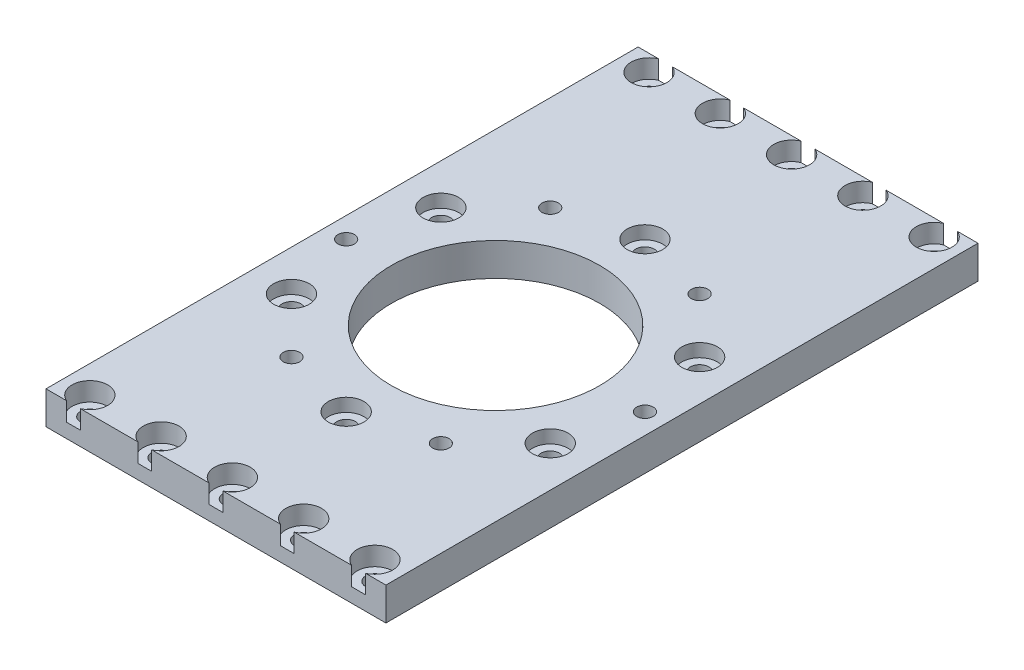
SolidWorks part; units mm, degrees
material "6061-T6 (SS)"
ref_plane "Front Plane" through (0, 0, 0) normal (0, 0, 1) x (1, 0, 0)
ref_plane "Top Plane" through (0, 0, 0) normal (0, 1, 0) x (1, 0, 0)
ref_plane "Right Plane" through (0, 0, 0) normal (1, 0, 0) x (0, 0, -1)
sketch "Sketch1" plane through (0, 0, 0) normal (0, 1, 0) x (1, 0, 0)
  circle A0 centre (0, 0) radius 31
  circle A1 centre (0, 0) radius 19
  dimension "D1" = 62
  dimension "D2" = 38
extrude "Boss-Extrude1" add sketch "Sketch1" along normal blind 6
sketch "Sketch2" plane through (0, 6, 0) normal (0, 1, 0) x (1, 0, 0)
  circle A0 centre (0, 0) radius 27.25 construction
  point P4 (0, 27.25)
  point P10 (23.5992, 13.625)
  point P11 (23.5992, -13.625)
  point P12 (0, -27.25)
  point P13 (-23.5992, -13.625)
  point P14 (-23.5992, 13.625)
  dimension "D1" = 54.5
  dimension "D2" = 6
hole_wizard "CBORE for M3 Hex Socket Thin Head Cap Screw1" positions "Sketch2" profile "Sketch3" counterbore size "M3" standard "DIN" end condition through all
sketch "Sketch3" plane through (-23.5992, 6, -13.625) normal (1, 0, 0) x (0, 0, 1)
  line L0 (0, 0) -> (0, 6)
  line L1 (0, 6) -> (1.7, 6)
  line L3 (1.7, 6) -> (1.7, 2.4)
  line L4 (1.7, 2.4) -> (3.25, 2.4)
  line L5 (3.25, 2.4) -> (3.25, 0)
  line L7 (3.25, 0) -> (0, 0)
  line L11 (0, -6.35) -> (0, 107.95) construction
  dimension "Thru Hole Dia." = 3.4
  dimension "Thru Hole Depth" = 6
  dimension "C'Bore Dia." = 6.5
  dimension "C'Bore Depth" = 2.4
sketch "Sketch4" plane through (0, 6, 0) normal (0, 1, 0) x (1, 0, 0)
  circle A0 centre (0, 0) radius 27.25
  point P6 (-27.25, 0)
  point P12 (-13.625, 23.5992)
  point P13 (13.625, 23.5992)
  point P14 (27.25, 0)
  point P15 (13.625, -23.5992)
  point P16 (-13.625, -23.5992)
  dimension "D1" = 6
hole_wizard "Ø3.0mm Dowel Hole1" positions "Sketch4" profile "Sketch5" hole size "Ø3.0" standard "DIN" end condition through all
sketch "Sketch5" plane through (-13.625, 6, 23.5992) normal (1, 0, 0) x (0, 0, 1)
  line L0 (0, 0) -> (0, 6)
  line L1 (0, 6) -> (1.5, 6)
  line L2 (1.5, 6) -> (1.5, 0)
  line L5 (1.5, 0) -> (0, 0)
  line L11 (0, -6.35) -> (0, 107.95) construction
  dimension "Thru Hole Dia." = 3
  dimension "Thru Hole Depth" = 6
sketch "Sketch6" plane through (0, 6, 0) normal (0, 1, 0) x (1, 0, 0)
  line L0 (-31, 0) -> (-31, -51)
  line L1 (-31, -51) -> (31, -51)
  line L2 (31, -51) -> (31, 0)
  circle A0 centre (0, 0) radius 31 construction
  arc A1 (-31, 0) -> (31, 0) centre (0, 0) ccw
  dimension "D1" = 51
extrude "Boss-Extrude2" add sketch "Sketch6" against normal up to surface (6 mm away) up to face at (-27.25, 0, 1.5)
sketch "Sketch10" plane through (0, 6, 0) normal (0, 1, 0) x (1, 0, 0)
  line L0 (-31, 0) -> (-31, 57)
  line L1 (-31, 57) -> (31, 57)
  line L2 (31, 57) -> (31, 0)
  arc A0 (31, 0) -> (-31, 0) centre (0, 0) ccw construction
  arc A1 (31, 0) -> (-31, 0) centre (0, 0) ccw
  dimension "D1" = 57
extrude "Boss-Extrude3" add sketch "Sketch10" against normal up to surface (6 mm away) up to face at (-27.25, 0, 1.5)
sketch "Sketch11" plane through (0, 6, 0) normal (0, 1, 0) x (1, 0, 0)
  line L0 (31, 57) -> (-31, 57) construction
  line L1 (-31, 57) -> (-31, -51) construction
  line L2 (-31, -51) -> (31, -51) construction
  point P0 (-26, 54)
  point P13 (-13, 54)
  point P14 (0, 54)
  point P15 (13, 54)
  point P16 (26, 54)
  point P19 (0, -48)
  point P31 (13, -48)
  point P32 (26, -48)
  point P33 (0, -48)
  point P34 (13, -48)
  point P35 (-13, -48)
  point P36 (0, -48)
  point P37 (-13, -48)
  point P38 (-26, -48)
  dimension "D3" = 3
  dimension "D1" = 3
  dimension "D2" = 5
  dimension "D4" = 3
hole_wizard "CBORE for M3 Hex Socket Head Cap Screw1" positions "Sketch11" profile "Sketch12" counterbore size "M3" standard "DIN" end condition through all
sketch "Sketch12" plane through (-26, 6, -54) normal (1, 0, 0) x (0, 0, 1)
  line L0 (0, 0) -> (0, 6)
  line L1 (0, 6) -> (1.7, 6)
  line L3 (1.7, 6) -> (1.7, 3.4)
  line L4 (1.7, 3.4) -> (3.25, 3.4)
  line L5 (3.25, 3.4) -> (3.25, 0)
  line L7 (3.25, 0) -> (0, 0)
  line L11 (0, -6.35) -> (0, 107.95) construction
  dimension "Thru Hole Dia." = 3.4
  dimension "Thru Hole Depth" = 6
  dimension "C'Bore Dia." = 6.5
  dimension "C'Bore Depth" = 3.4
